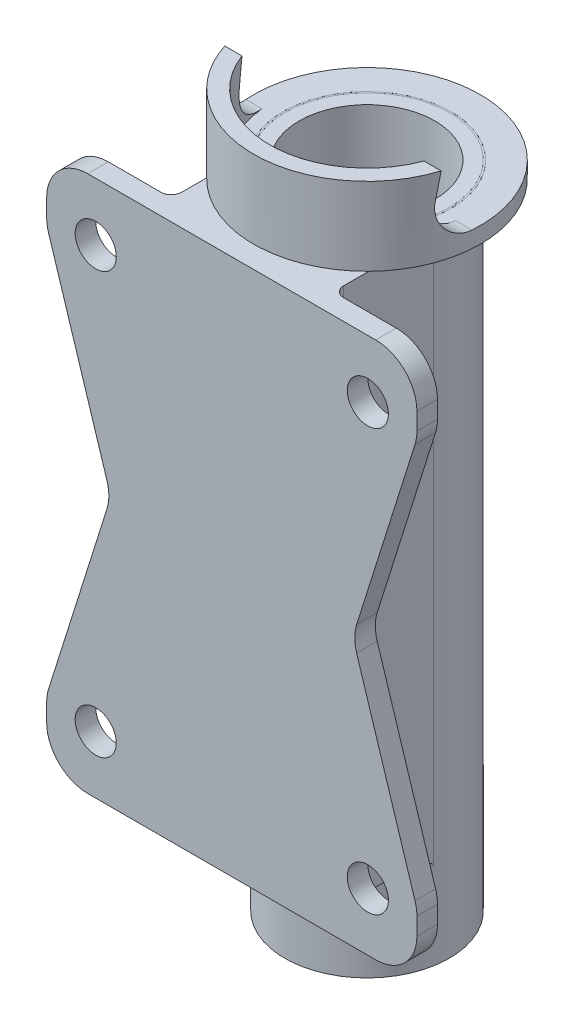
SolidWorks part; units mm, degrees
note: The reader was unsure of these and kept them because the rebuilt part matched: shared geometry of "Sketch26<3>".
other "pipe"
other "shoe_support"
other "angle_limit"
other "Weld Folder"
material "6063-O"
ref_plane "Front Plane" through (0, 0, 0) normal (0, 0, 1) x (1, 0, 0)
ref_plane "Top Plane" through (0, 0, 0) normal (0, 1, 0) x (1, 0, 0)
ref_plane "Right Plane" through (0, 0, 0) normal (1, 0, 0) x (0, 0, -1)
sketch "Sketch11" plane through (0, 0, 0) normal (0, 0, 1) x (1, 0, 0)
  line L0 (0, 0) -> (0, 109.6398) construction
  line L1 (0, 0) -> (-89.1372, 0) construction
sketch "Sketch12" plane through (0, 0, 0) normal (0, 0, 1) x (1, 0, 0)
  line L0 (-25.4, 0) -> (-25.4, 203.2)
  line L1 (200000, 0) -> (-200089.1372, 0) construction
  line L4 (-20.955, 0) -> (-25.4, 0)
  line L5 (-20.955, 0) -> (-20.955, 38.1)
  line L6 (-20.955, 38.1) -> (-19.177, 38.1)
  line L7 (-19.177, 38.1) -> (-19.177, 165.1)
  line L8 (-19.177, 165.1) -> (-20.955, 165.1)
  line L9 (-20.955, 165.1) -> (-20.955, 203.2)
  line L10 (-20.955, 203.2) -> (-25.4, 203.2)
  line L12 (0, -200000) -> (0, 200109.6398) construction
  line L13 (-20.955, 203.2) -> (-15.875, 203.2) construction
  line L14 (-15.875, 203.2) -> (-15.875, 0) construction
  line L15 (-15.875, 0) -> (-20.955, 0) construction
  dimension "D1" = 25.4
  dimension "D2" = 20.955
  dimension "D3" = 19.177
  dimension "D4" = 38.1
  dimension "D5" = 203.2
  dimension "D6" = 4.445
  dimension "D7" = 15.875
revolve "Revolve1" add sketch "Sketch12" angle 360 about L0
ref_plane "mideplane" through (0, 101.6, 0) normal (0, -1, 0) x (-1, 0, 0)
ref_plane "top pipe plane" through (0, 30, 0) normal (0, -1, 0) x (-1, 0, 0)
ref_plane "bottom pipe plane" through (0, 183.2, 0) normal (0, 1, 0) x (1, 0, 0)
ref_plane "pipe support midplane" through (0, 106.6, 0) normal (0, -1, 0) x (-1, 0, 0)
sketch "Sketch14" plane through (0, 30, 0) normal (0, -1, 0) x (-1, 0, 0)
  line L0 (0, 0) -> (-25.4, 0) construction
  line L1 (0, 0) -> (25.4, 0) construction
  line L7 (-25, -35.4) -> (25, -35.4)
  line L9 (25, -35.4) -> (25, -4.49)
  line L10 (-25, -35.4) -> (-25, -4.49)
  circle A0 centre (0, 0) radius 25.4 construction
  circle A1 centre (0, 0) radius 25.4
  circle A2 centre (0, 0) radius 25.4 construction
  arc A3 (25.4, 0) -> (-25.4, 0) centre (0, 0) cw
  dimension "D1" = 0
  dimension "D2" = 10
  dimension "D3" = 50
extrude "Boss-Extrude1" add sketch "Sketch14" against normal blind 3.175 separate body contours A1 L10 L7 L9
sketch "Sketch15" plane through (0, 33.175, 0) normal (0, 1, 0) x (1, 0, 0)
  line L0 (25, -35.4) -> (-25, -35.4) construction
  line L4 (-1.5875, -35.4) -> (1.5875, -35.4)
  line L5 (-1.5875, -35.4) -> (-1.5875, -25.3503)
  line L7 (1.5875, -35.4) -> (1.5875, -25.3503)
  circle A1 centre (0, 0) radius 25.4 construction
  circle A2 centre (0, 0) radius 25.4
  dimension "D1" = 3.175
extrude "Boss-Extrude4" add sketch "Sketch15" along normal up to surface (150.025 mm away) contours A2 L5 L4 L7 up to plane "bottom pipe plane"
sketch "Sketch17" plane through (0, 183.2, 0) normal (0, 1, 0) x (1, 0, 0)
  line L3 (25, -35.4) -> (25, -4.49)
  line L4 (-25, -35.4) -> (25, -35.4)
  line L5 (-25, -4.49) -> (-25, -35.4)
  line L9 (25, -35.4) -> (25, -4.49)
  line L10 (-25, -35.4) -> (25, -35.4)
  line L11 (-25, -4.49) -> (-25, -35.4)
  arc A1 (-25, -4.49) -> (25, -4.49) centre (0, 0) ccw
  arc A3 (-25, -4.49) -> (25, -4.49) centre (0, 0) ccw
  dimension "D1" = 0
extrude "Boss-Extrude5" add sketch "Sketch17" along normal blind 3.175
sketch "Sketch18" plane through (0, 0, 35.4) normal (0, 0, 1) x (1, 0, 0)
  line L1 (57.15, 30) -> (-57.15, 30)
  line L2 (57.15, 30) -> (57.15, 203.2)
  line L4 (-57.15, 30) -> (-57.15, 203.2)
  line L5 (20.955, 203.2) -> (-20.955, 203.2) construction
  line L6 (-57.15, 203.2) -> (57.15, 203.2)
  line L7 (25.4, 203.2) -> (-25.4, 203.2) construction
  line L8 (0, 30) -> (0, 203.2) construction
  line L10 (46.15, 116.6) -> (-46.15, 116.6) construction
  line L11 (46.15, 47.175) -> (-46.15, 47.175) construction
  line L12 (46.15, 47.175) -> (46.15, 186.025) construction
  line L13 (46.15, 186.025) -> (-46.15, 186.025) construction
  line L14 (-46.15, 47.175) -> (-46.15, 186.025) construction
  line L15 (25, 30) -> (-25, 30) construction
  circle A0 centre (-46.15, 47.175) radius 5 construction
  circle A1 centre (-46.15, 47.175) radius 8 construction
  point P10 (46.15, 116.6)
  point P12 (-46.15, 116.6)
  point P13 (0, 203.2)
  point P21 (0, 116.6)
  line M9 (25, 30) -> (25, 33.175)
  line M19 (-25, 33.175) -> (-25, 30)
  line M35 (-25, 30) -> (25, 30)
  line M36 (25, 33.175) -> (1.5875, 33.175)
  line M38 (-1.5875, 33.175) -> (-25, 33.175)
  line M39 (1.5875, 33.175) -> (1.5875, 183.2)
  line M41 (-1.5875, 183.2) -> (-1.5875, 33.175)
  line M42 (1.5875, 183.2) -> (25, 183.2)
  line M43 (25, 183.2) -> (25, 186.375)
  line M44 (25, 186.375) -> (-25, 186.375)
  line M45 (-25, 186.375) -> (-25, 183.2)
  line M46 (-25, 183.2) -> (-1.5875, 183.2)
  dimension "D4" = 10
  dimension "D5" = 16
  dimension "D6" = 6
  dimension "D7" = 9.175
  dimension "D1" = 114.3
extrude "Boss-Extrude6" add sketch "Sketch18" along normal blind 6.35 contours L4 M38 M41 M46 | L2 M36 M42 M39 | M19 M35 M9 M36 M39 M42 M43 M44 M45 M46 M41 M38
sketch "Sketch30" plane through (0, 106.6, 0) normal (0, -1, 0) x (-1, 0, 0)
  line L3 (25, -35.4) -> (25, -4.49)
  line L4 (-25, -35.4) -> (25, -35.4)
  line L5 (-25, -4.49) -> (-25, -35.4)
  line L6 (25, -35.4) -> (25, -4.49)
  line L8 (-25, -4.49) -> (-25, -35.4)
  line L9 (-25, -35.4) -> (25, -35.4)
  arc A1 (-25, -4.49) -> (25, -4.49) centre (0, 0) ccw
  arc A2 (-25, -4.49) -> (25, -4.49) centre (0, 0) ccw
  dimension "D1" = 0
extrude "Boss-Extrude9" add sketch "Sketch30" along normal blind 1.5875 and the other way blind 1.5875
sketch "Sketch29" plane through (0, 0, 0) normal (0, -1, 0) x (1, 0, 0)
  circle A0 centre (0, 0) radius 20.955 construction
  circle A1 centre (0, 0) radius 20.955 construction
ref_plane "Plane4" through (0, 200.7, 0) normal (0, 1, 0) x (1, 0, 0)
sketch "Sketch25" plane through (0, 200.7, 0) normal (0, 1, 0) x (1, 0, 0)
  line L0 (0, -2.5) -> (34.9106, -2.5) construction
  line L1 (0, 2.5) -> (34.9106, 2.5) construction
  line L2 (0, 0) -> (35, 0) construction
  circle A0 centre (0, 0) radius 25.4 construction
  circle A1 centre (0, 0) radius 25.4 construction
  circle A2 centre (0, 0) radius 35 construction
  circle A3 centre (0, 0) radius 25.9 construction
  circle A4 centre (0, 0) radius 2.5 construction
  dimension "D1" = 0.5
  dimension "D2" = 70
  dimension "D3" = 5
sketch "Sketch26" plane through (0, 200.7, 0) normal (0, 1, 0) x (1, 0, 0)
  line L0 (34.9106, -2.5) -> (-34.9106, -2.5)
  circle A0 centre (0, 0) radius 25.9 construction
  circle A1 centre (0, 0) radius 35 construction
  circle A2 centre (0, 0) radius 25.9
  circle A3 centre (0, 0) radius 35
  arc A4 (29.8957, -2.5) -> (-29.8957, -2.5) centre (0, 0) cw
  point P0 (34.9106, -2.5)
  dimension "D1" = 5
extrude "Boss-Extrude7" add sketch "Sketch26" against normal blind 5 separate body
extrude "Boss-Extrude8" add sketch "Sketch26<3>" along normal blind 19.05 contours L0 A4 A3
sketch "Sketch26<3>" plane through (0, 200.7, 0) normal (0, 1, 0) x (1, 0, 0) same geometry as "Sketch26"
sketch "Sketch33" plane through (0, 0, 0) normal (1, 0, 0) x (0, 0, -1)
  line L0 (-2.5, 219.75) -> (-35, 219.75) construction
  line L1 (-2.9921, 219.75) -> (-2.5, 219.75)
  line L3 (35, 200.7) -> (-2.5, 200.7) construction
  line L5 (-11.8866, 211.8865) -> (-10.5, 219.75)
  line L8 (-2.5, 219.75) -> (-2.5, 200.7) construction
  line L9 (-2.5, 219.75) -> (-30, 219.75) construction
  line L10 (-2.5, 219.75) -> (-10.5, 219.75)
  line L11 (-2.5, 219.75) -> (-2.5, 200.7)
  arc A1 (-2.5, 200.7) -> (-11.8866, 211.8865) centre (-2.5, 210.2314) cw
  arc A2 (-11.8866, 211.8865) -> (-2.9921, 219.75) centre (-2.5, 210.2314) cw construction
  dimension "D1" = 8
  dimension "D2" = 100
extrude "Cut-Extrude3" cut sketch "Sketch33" against normal through all both and the other way through all contours A1 L11 L1 L10 L5
sketch "Sketch34" plane through (0, 33.175, 0) normal (0, 1, 0) x (1, 0, 0)
  line L3 (-25, -35.4) -> (-1.5875, -35.4)
  line L4 (-1.5875, -35.4) -> (-1.5875, -25.3503)
  line L5 (-25, -4.49) -> (-25, -35.4)
  line L6 (-25, -35.4) -> (-1.5875, -35.4)
  line L7 (-1.5875, -35.4) -> (-1.5875, -25.3503)
  line L8 (-25, -4.49) -> (-25, -35.4)
  line L9 (1.5875, -25.3503) -> (1.5875, -35.4)
  line L10 (1.5875, -35.4) -> (25, -35.4)
  line L11 (25, -35.4) -> (25, -4.49)
  line L12 (1.5875, -25.3503) -> (1.5875, -35.4)
  line L13 (1.5875, -35.4) -> (25, -35.4)
  line L14 (25, -35.4) -> (25, -4.49)
  arc A1 (-25, -4.49) -> (-1.5875, -25.3503) centre (0, 0) ccw
  arc A2 (-25, -4.49) -> (-1.5875, -25.3503) centre (0, 0) ccw
  arc A3 (1.5875, -25.3503) -> (25, -4.49) centre (0, 0) ccw
  arc A4 (1.5875, -25.3503) -> (25, -4.49) centre (0, 0) ccw
  dimension "D1" = 0
  dimension "D2" = 0
extrude "Boss-Extrude10" add sketch "Sketch34" along normal up to surface (150.025 mm away) up to face at (14.1946, 183.2, 26.1711)
sketch "Sketch35" plane through (0, 186.375, 0) normal (0, 1, 0) x (1, 0, 0)
  line L5 (-25, -35.4) -> (25, -35.4)
  line L6 (-25, -35.4) -> (25, -35.4)
  line L10 (25, -35.4) -> (25, -4.49)
  line L11 (-25, -4.49) -> (-25, -35.4)
  line L17 (25, -35.4) -> (25, -4.49)
  line L18 (-25, -4.49) -> (-25, -35.4)
  arc A4 (-25, -4.49) -> (25, -4.49) centre (0, 0) ccw
  arc A7 (-25, -4.49) -> (25, -4.49) centre (0, 0) ccw
  dimension "D1" = 0
extrude "Boss-Extrude11" add sketch "Sketch35" along normal up to surface (9.325 mm away) up to face at (0, 195.7, 25.9)
sketch "Sketch36" plane through (57.15, 0, 0) normal (1, 0, 0) x (0, 0, -1)
  line L0 (-41.75, 30) -> (-41.75, 203.2) construction
  line L1 (-35.4, 203.2) -> (-41.75, 203.2)
  line L2 (-35.4, 203.2) -> (-35.4, 195.7)
  line L3 (-35.4, 195.7) -> (-41.75, 195.7)
  line L4 (-41.75, 203.2) -> (-41.75, 195.7)
  line L5 (-35.4, 195.7) -> (-24.4949, 195.7) construction
extrude "Cut-Extrude4" cut sketch "Sketch36" against normal through all
fillet "Fillet1" radius 3.175 3 edges at (0, 30, 25.4) (-25, 112.85, 35.4) (25, 112.85, 35.4)
sketch "Sketch37" plane through (0, 0, 35.4) normal (0, 0, -1) x (-1, 0, 0)
  line L0 (0, 30) -> (0, 195.7) construction
  line L1 (-35, 195.7) -> (35, 195.7) construction
  line L2 (-57.15, 112.85) -> (57.15, 112.85) construction
  line L3 (-57.15, 30) -> (-57.15, 195.7) construction
  line L4 (57.15, 30) -> (57.15, 195.7) construction
  line L5 (-57.15, 175.7) -> (-37.3335, 112.85)
  line L6 (-57.15, 175.7) -> (-57.15, 50)
  line L8 (-57.15, 50) -> (-37.3335, 112.85)
  line L9 (57.15, 50) -> (37.3335, 112.85)
  line L11 (57.15, 175.7) -> (57.15, 50)
  line L12 (57.15, 175.7) -> (37.3335, 112.85)
  dimension "D1" = 20
  dimension "D2" = 17.5
extrude "Cut-Extrude5" cut sketch "Sketch37" against normal through all contours L12 L11 L9 | L5 L6 L8
fillet "Fillet2" radius 12.7 10 edges at (-57.15, 195.7, 38.575) (-57.15, 175.7, 38.575) (-37.3335, 112.85, 38.575) (-57.15, 50, 38.575) (-57.15, 30, 38.575) (57.15, 30, 38.575) (57.15, 50, 38.575) (37.3335, 112.85, 38.575) (57.15, 175.7, 38.575) (57.15, 195.7, 38.575)
sketch "Sketch38" plane through (0, 0, 35.4) normal (0, 0, -1) x (-1, 0, 0)
  line L0 (0, 30) -> (0, 195.7) construction
  line L1 (-35, 195.7) -> (35, 195.7) construction
  line L5 (25, 30) -> (28.175, 30) construction
  line L6 (-37.9498, 112.85) -> (37.9498, 112.85) construction
  circle A0 centre (-42, 177.85) radius 6.35
  arc A8 (-38.5376, 109.031) -> (-38.5376, 116.669) centre (-50.6498, 112.85) ccw construction
  arc A9 (38.5376, 116.669) -> (38.5376, 109.031) centre (50.6498, 112.85) ccw construction
  circle A10 centre (42, 177.85) radius 6.35
  circle A11 centre (42, 47.85) radius 6.35
  circle A12 centre (-42, 47.85) radius 6.35
  dimension "D1" = 12.7
  dimension "D2" = 42
  dimension "D3" = 65
extrude "Cut-Extrude6" cut sketch "Sketch38" against normal through all
sketch "Sketch41" plane through (0, 200.7, 0) normal (0, 1, 0) x (1, 0, 0)
  circle A0 centre (0, 0) radius 25.4
  circle A1 centre (0, 0) radius 25.4 construction
extrude "Cut-Extrude8" cut sketch "Sketch41" along normal through all
surface "Surface-Fill1"
